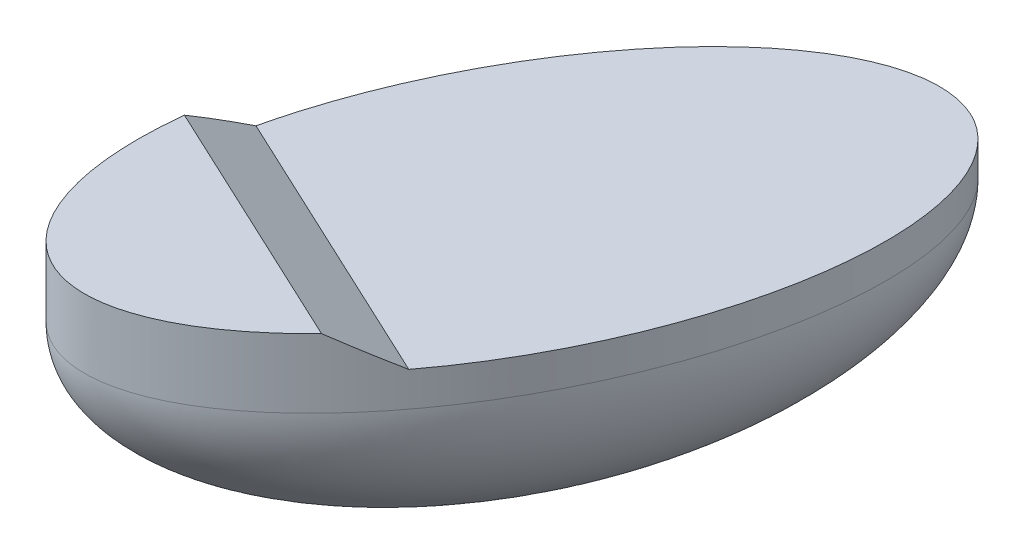
SolidWorks part; units mm, degrees
ref_plane "Front Plane" through (0, 0, 0) normal (0, 0, 1) x (1, 0, 0)
ref_plane "Top Plane" through (0, 0, 0) normal (0, 1, 0) x (1, 0, 0)
ref_plane "Right Plane" through (0, 0, 0) normal (1, 0, 0) x (0, 0, -1)
sketch "Sketch1" plane through (0, 0, 0) normal (0, 1, 0) x (1, 0, 0)
  ellipse E0 centre (0, 0) end of major axis (-8478.8021, -18113.8045) minor radius 10000
extrude "Boss-Extrude1" add sketch "Sketch1" along normal blind 2000
sketch "Sketch2" plane through (0, 0, 0) normal (0, -1, 0) x (1, 0, 0)
  line L0 (-8478.8021, 18113.8045) -> (8478.8021, -18113.8045)
  ellipse E0 centre (0, 0) end of major axis (8478.8021, -18113.8045) minor radius 10000 construction
  ellipse E2 centre (0, 0) end of major axis (8478.8021, -18113.8045) minor radius 10000
  ellipse E3 centre (0, 0) end of major axis (8478.8021, -18113.8045) minor radius 10000 (8478.8021, -18113.8045) -> (-8478.8021, 18113.8045) ccw
  dimension "D1" = 0
revolve "Revolve1" add sketch "Sketch2" angle 180 about L0
sketch "Sketch3" plane through (0, 2000, 0) normal (0, 1, 0) x (1, 0, 0)
  line L0 (-8478.8021, -18113.8045) -> (8478.8021, 18113.8045) construction
  line L1 (-11654.3199, -3194.4513) -> (5012.0967, -10995.7527)
  ellipse E1 centre (0, 0) end of major axis (8478.8021, 18113.8045) minor radius 10000
  ellipse E2 centre (0, 0) end of major axis (8478.8021, 18113.8045) minor radius 10000
  ellipse M4 centre (0, 0) end of major axis (8478.8021, 18113.8045) minor radius 10000
  dimension "D2" = 90
  dimension "D1" = 0
extrude "Boss-Extrude2" add sketch "Sketch3" along normal blind 2000 contours L0 L1 M4 | L0 E2 L1 region at (-8756.6706, 2000, 10094.5073) region at (-2142.6603, 2000, 13190.427)
chamfer "Chamfer1" distance 2000 angle 60 1 edges at (-3321.1116, 4000, 7095.102) first distance on face at (-3321.1116, 3000, 7095.102)
